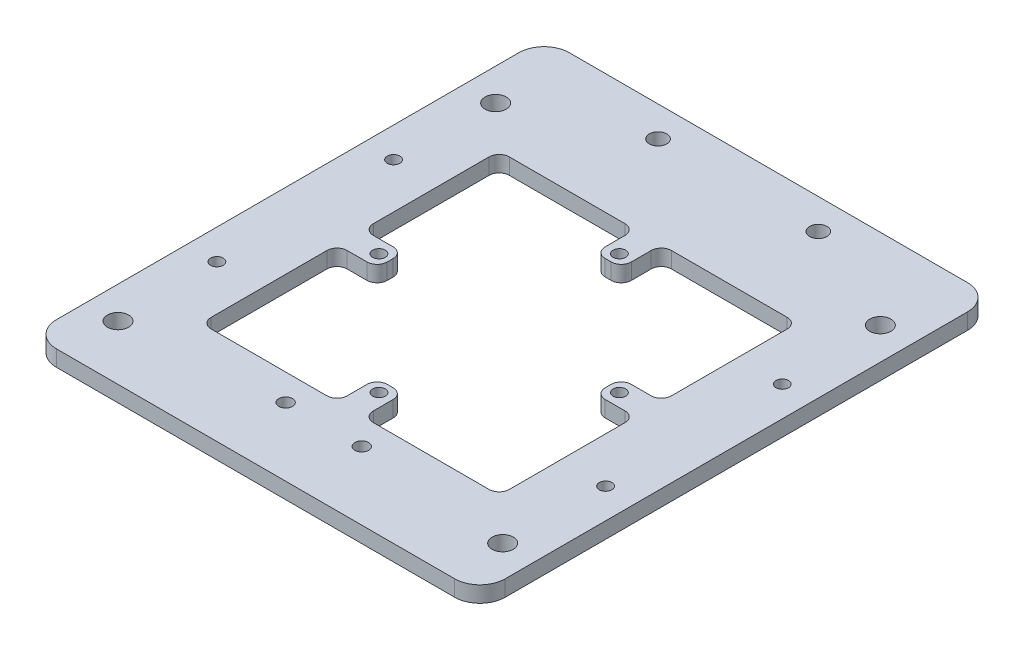
SolidWorks part; units mm, degrees
ref_plane "Front Plane" through (0, 0, 0) normal (0, 0, 1) x (1, 0, 0)
ref_plane "Top Plane" through (0, 0, 0) normal (0, 1, 0) x (1, 0, 0)
ref_plane "Right Plane" through (0, 0, 0) normal (1, 0, 0) x (0, 0, -1)
sketch "Sketch2" plane through (0, 0, 0) normal (0, 1, 0) x (1, 0, 0)
  line L0 (58.0244, -30.9317) -> (-20.8765, -30.931)
  line L1 (-25.8765, -25.9309) -> (-25.8756, 65.6691)
  line L2 (-20.8755, 70.669) -> (58.0245, 70.6683)
  line L3 (63.0245, 65.6683) -> (63.0245, -25.9317)
  line L4 (40.1645, -4.2611) -> (-3.0155, -4.2611)
  line L6 (-3.0155, 38.9189) -> (40.1645, 38.9189)
  line L7 (40.1645, 38.9189) -> (40.1645, -4.2611)
  line L11 (-3.0155, 38.9189) -> (-3.0155, -4.2611)
  arc A0 (63.0245, 65.6683) -> (58.0245, 70.6683) centre (58.0245, 65.6683) ccw
  arc A1 (58.0244, -30.9317) -> (63.0245, -25.9317) centre (58.0245, -25.9317) ccw
  arc A2 (-20.8765, -30.931) -> (-25.8765, -25.9309) centre (-20.8765, -25.931) cw
  arc A3 (-20.8755, 70.669) -> (-25.8756, 65.6691) centre (-20.8756, 65.669) ccw
  point P0 (18.5745, -4.2611)
  point P1 (-21.2336, 35.0739)
  point P2 (-3.0155, 17.3289)
  point P7 (63.0245, 70.6682)
  point P20 (-25.8765, -30.9309)
  point P23 (-25.8755, 70.6691)
  dimension "D3" = 5
  dimension "D2" = 43.18
  dimension "D4" = 48.26
  dimension "D5" = 43.18
  dimension "D6" = 43.18
  dimension "D7" = 44.45
  dimension "D8" = 101.6
  dimension "D9" = 43.18
  dimension "D18" = 88.9
  dimension "D19" = 101.6
extrude "Aluminum plate" add sketch "Sketch2" along normal blind 3.175
ref_axis "Axis4" through (18.5745, 3.175, 4.2611) along (0, 0, -1)
ref_axis "Axis2" through (40.1645, 3.175, -17.3289) along (-1, 0, 0)
ref_plane "Plane8" through (0, 0, -17.3289) normal (0, 0, 1) x (1, 0, 0)
ref_plane "Plane10" through (18.5745, 0, 0) normal (1, 0, 0) x (0, 0, -1)
ref_axis "Axis8" through (18.5745, 62.6713, -17.3289) along (0, -1, 0)
hole_wizard "Tap Drill for M3x0.5 Tap1" positions "Sketch13" profile "Sketch12" hole size "M3x0.5" standard "Ansi Metric"
sketch "Sketch13" plane through (0, 3.175, 0) normal (0, 1, 0) x (-1, 0, 0)
  line L0 (25.8756, -65.6691) -> (25.8765, 25.9309) construction
  point P1 (19.9259, -34.9096)
  dimension "D1" = 5.95
sketch "Sketch12" plane through (-19.9259, 3.175, -34.9096) normal (1, 0, 0) x (0, 0, 1)
  line L0 (0, 0) -> (0, 26.1511)
  line L1 (0, 26.1511) -> (1.25, 25.4)
  line L2 (1.25, 25.4) -> (1.25, 0)
  line L5 (1.25, 0) -> (0, 0)
  line L10 (0, 26.1511) -> (-1.25, 25.4) construction
  line L11 (0, -6.35) -> (0, 107.95) construction
  dimension "Hole Dia." = 2.5
  dimension "Hole Depth" = 25.4
  dimension "Drill Angle" = 118
pattern_linear "LPattern1" count 2 spacing 35 along (0, 0, 1) count 2 spacing 77 along (1, 0, 0) of "Tap Drill for M3x0.5 Tap1"
hole_wizard "Tap Drill for M3x0.5 Tap2" positions "Sketch15" profile "Sketch14" hole size "M3x0.5" standard "Ansi Metric"
sketch "Sketch15" plane through (0, 3.175, 0) normal (0, 1, 0) x (-1, 0, 0)
  line L0 (-18.5745, 4.2611) -> (-18.5745, -38.9189) construction
  point P0 (-42.3845, -17.3292)
  dimension "D1" = 23.81
sketch "Sketch14" plane through (42.3845, 3.175, -17.3292) normal (1, 0, 0) x (0, 0, 1)
  line L0 (0, 0) -> (0, 26.1511)
  line L1 (0, 26.1511) -> (1.25, 25.4)
  line L2 (1.25, 25.4) -> (1.25, 0)
  line L5 (1.25, 0) -> (0, 0)
  line L10 (0, 26.1511) -> (-1.25, 25.4) construction
  line L11 (0, -6.35) -> (0, 107.95) construction
  dimension "Hole Dia." = 2.5
  dimension "Hole Depth" = 25.4
  dimension "Drill Angle" = 118
pattern_circular "CirPattern1" count 4 every 90 about axis through (18.5745, 62.6713, -17.3289) along (0, -1, 0) of "Tap Drill for M3x0.5 Tap2"
hole_wizard "Tap Drill for M5x0.8 Tap1" positions "Sketch17" profile "Sketch16" hole size "M5x0.8" standard "Ansi Metric"
sketch "Sketch17" plane through (0, 0, 0) normal (0, -1, 0) x (1, 0, 0)
  line L0 (-25.8756, -65.6691) -> (-25.8765, 25.9309) construction
  line L1 (-20.8765, 30.931) -> (58.0244, 30.9317) construction
  line L2 (-3.0155, -38.9189) -> (-3.0155, 4.2611) construction
  line L3 (-20.8765, 30.931) -> (58.0244, 30.9317) construction
  point P5 (-19.5257, -54.7305)
  point P14 (56.6743, -54.7298)
  point P16 (56.6736, 20.0732)
  point P18 (-19.5264, 20.0725)
  point P25 (-3.0155, -17.3289)
  dimension "D1" = 74.803
  dimension "D2" = 74.803
  dimension "D3" = 76.2
  dimension "D4" = 76.2
  dimension "D5" = 6.35
  dimension "D6" = 10.8585
  dimension "D7" = 6.35
  dimension "D8" = 10.8585
  dimension "D9" = 48.26
sketch "Sketch16" plane through (-19.5257, 0, -54.7305) normal (1, 0, 0) x (0, 0, -1)
  line L0 (0, 0) -> (0, 26.6618)
  line L1 (0, 26.6618) -> (2.1, 25.4)
  line L2 (2.1, 25.4) -> (2.1, 0)
  line L5 (2.1, 0) -> (0, 0)
  line L10 (0, 26.6618) -> (-2.1, 25.4) construction
  line L11 (0, -6.35) -> (0, 107.95) construction
  dimension "Hole Dia." = 4.2
  dimension "Hole Depth" = 25.4
  dimension "Drill Angle" = 118
hole_wizard "Tap Drill for #8-32 Tap1" positions "Sketch19" profile "Sketch18" hole size "#8-32" standard "Ansi Inch"
sketch "Sketch19" plane through (0, 3.175, 0) normal (0, 1, 0) x (-1, 0, 0)
  line L0 (25.8756, -65.6691) -> (25.8765, 25.9309) construction
  line L3 (-58.0245, -70.6683) -> (20.8755, -70.669) construction
  point P0 (-2.6994, -64.6688)
  point P1 (-34.4494, -64.6685)
  dimension "D1" = 31.75
  dimension "D2" = 28.575
  dimension "D3" = 6
  dimension "D4" = 6
sketch "Sketch18" plane through (2.6994, 3.175, -64.6688) normal (1, 0, 0) x (0, 0, 1)
  line L0 (0, 0) -> (0, 13.7378)
  line L1 (0, 13.7378) -> (1.7272, 12.7)
  line L2 (1.7272, 12.7) -> (1.7272, 0)
  line L5 (1.7272, 0) -> (0, 0)
  line L10 (0, 13.7378) -> (-1.7272, 12.7) construction
  line L11 (0, -6.35) -> (0, 107.95) construction
  dimension "Hole Dia." = 3.4544
  dimension "Hole Depth" = 12.7
  dimension "Drill Angle" = 118
sketch "Sketch24" plane through (0, 3.175, 0) normal (0, 1, 0) x (1, 0, 0)
  line L0 (21.1645, 40.9189) -> (21.1645, 44.8564)
  line L1 (40.1645, 38.9189) -> (-3.0155, 38.9189) construction
  line L2 (23.1645, 46.8564) -> (46.102, 46.8564)
  line L3 (48.102, 44.8564) -> (48.102, 21.9189)
  line L4 (46.102, 19.9189) -> (42.1645, 19.9189)
  line L5 (40.1645, -4.2611) -> (40.1645, 38.9189) construction
  line L8 (40.1645, 17.9189) -> (40.1645, 17.3289)
  line L9 (40.1645, 17.3289) -> (-3.0155, 17.3289) construction
  line L10 (40.1645, 17.3289) -> (18.5745, 38.9189)
  line L11 (18.5745, 38.9189) -> (19.1645, 38.9189)
  arc A0 (46.102, 19.9189) -> (48.102, 21.9189) centre (46.102, 21.9189) ccw
  arc A1 (48.102, 44.8564) -> (46.102, 46.8564) centre (46.102, 44.8564) ccw
  arc A2 (23.1645, 46.8564) -> (21.1645, 44.8564) centre (23.1645, 44.8564) ccw
  arc A3 (40.1645, 17.9189) -> (42.1645, 19.9189) centre (42.1645, 17.9189) cw
  arc A4 (21.1645, 40.9189) -> (19.1645, 38.9189) centre (19.1645, 40.9189) cw
  point P12 (48.102, 19.9189)
  point P17 (21.1645, 46.8564)
  point P23 (40.1645, 19.9189)
  point P26 (21.1645, 38.9189)
  dimension "D5" = 2
  dimension "D3" = 2
  dimension "D1" = 7.9375
  dimension "D2" = 7.9375
extrude "Cut-Extrude1" cut sketch "Sketch24" against normal up to next
pattern_circular "CirPattern3" count 4 every 90 about axis through (18.5745, 62.6713, -17.3289) along (0, -1, 0) of "Cut-Extrude1"
hole_wizard "Tap Drill for #6-32 Tap1" positions "Sketch26" profile "Sketch25" hole size "#6-32" standard "Ansi Inch"
sketch "Sketch26" plane through (0, 3.175, 0) normal (0, 1, 0) x (-1, 0, 0)
  line L0 (25.8756, -65.6691) -> (25.8765, 25.9309) construction
  line L3 (20.8765, 30.931) -> (-58.0244, 30.9317) construction
  point P0 (-11.033, 17.4313)
  point P1 (-26.1142, 17.4313)
  dimension "D1" = 15.0812
  dimension "D2" = 36.9094
  dimension "D3" = 13.5
sketch "Sketch25" plane through (11.033, 3.175, 17.4313) normal (1, 0, 0) x (0, 0, 1)
  line L0 (0, 0) -> (0, 13.5127)
  line L1 (0, 13.5127) -> (1.3525, 12.7)
  line L2 (1.3525, 12.7) -> (1.3525, 0)
  line L5 (1.3525, 0) -> (0, 0)
  line L10 (0, 13.5127) -> (-1.3526, 12.7) construction
  line L11 (0, -6.35) -> (0, 107.95) construction
  dimension "Hole Dia." = 2.7051
  dimension "Hole Depth" = 12.7
  dimension "Drill Angle" = 118
equation "\"D7@Sketch2\" = \"D18@Sketch2\"/2"
equation "\"D2@Sketch17\" = \"D1@Sketch17\""
equation "\"D4@Sketch17\" = \"D3@Sketch17\""
equation "\"D5@Sketch17\" = (\"D18@Sketch2\"-\"D4@Sketch17\")/2"
equation "\"D6@Sketch17\" = \"D9@Sketch17\"-(\"D2@Sketch17\"/2)"
equation "\"D7@Sketch17\" = \"D5@Sketch17\""
equation "\"D8@Sketch17\" = \"D6@Sketch17\""
equation "\"D2@Sketch19\" = (\"D18@Sketch2\"-\"D1@Sketch19\")/2"
equation "\"D8@Sketch2\" = \"D19@Sketch2\""
equation "\"D4@Sketch19\" = \"D3@Sketch19\""
equation "\"D1@Sketch13\" = (\"D18@Sketch2\"-\"RD5@Annotations\")/2"
equation "\"D2@Sketch26\" = (\"D18@Sketch2\"-\"D1@Sketch26\")/2"
